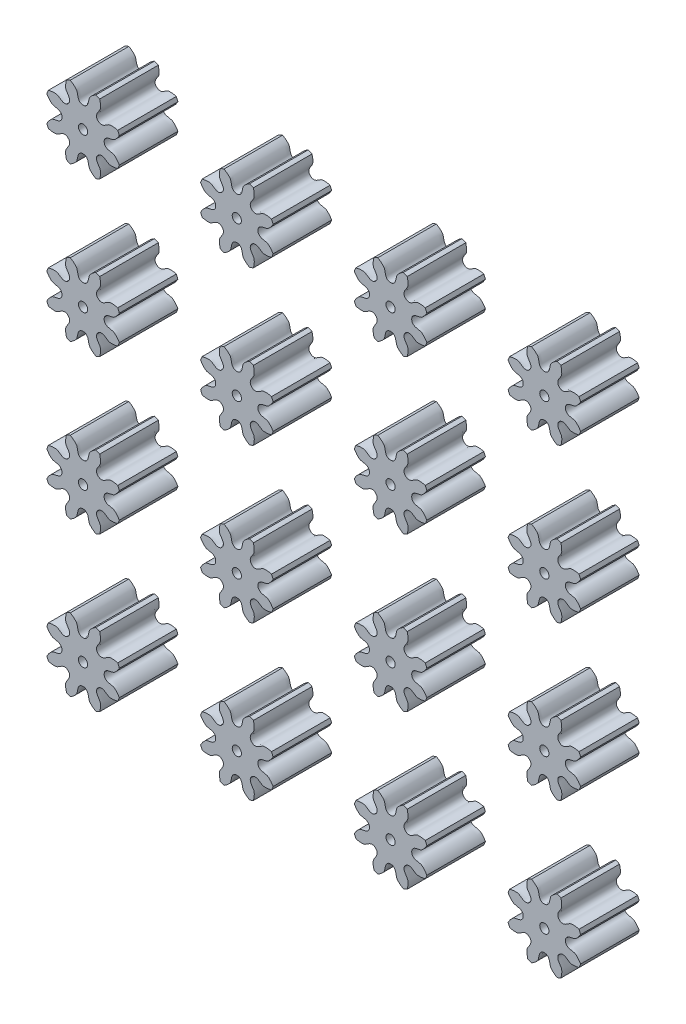
SolidWorks part; units mm, degrees
ref_plane "前视基准面" through (0, 0, 0) normal (0, 0, 1) x (1, 0, 0)
ref_plane "上视基准面" through (0, 0, 0) normal (0, 1, 0) x (1, 0, 0)
ref_plane "右视基准面" through (0, 0, 0) normal (1, 0, 0) x (0, 0, -1)
ref_axis "基准轴1" through (0, 0, 55) along (0, 0, -1)
sketch "SketchRevolveSpurGear1" plane through (0, 0, 0) normal (1, 0, 0) x (0, 0, -1)
  line L0 (0, 0) -> (1, 0) construction
  line L1 (-9.525, 0) -> (-9.525, 12.5)
  line L2 (-9.525, 12.5) -> (9.525, 12.5)
  line L3 (9.525, 12.5) -> (9.525, 0)
  line L4 (9.525, 0) -> (-9.525, 0)
revolve "SpurGear1" add sketch "SketchRevolveSpurGear1" angle 360 about L0
sketch "SketchToothSpurGear1" plane through (0, 0, 0) normal (0, 0, 1) x (1, 0, 0)
  arc A0 (11.8708, 4.2983) -> (11.8708, -4.2983) centre (0, 0) cw
  spline S0 degree 3 poles (11.8708, -4.2983) (11.7054, -3.9899) (11.4661, -3.6029) (11.1329, -3.1632) (10.9456, -2.9376) (10.7609, -2.7348) (10.581, -2.5534) (10.4063, -2.3946) (9.7527, -1.8246) (8.8695, -1.8284) (8.1725, -1.6298) (8.1519, -1.6237) (8.1313, -1.6175) (8.1108, -1.6111) (8.0904, -1.6045) (8.0701, -1.5977) (8.0499, -1.5908) (8.0297, -1.5837) (8.0096, -1.5764) (7.9897, -1.569) (7.9698, -1.5614) (7.95, -1.5536) (7.9302, -1.5456) (7.9106, -1.5375) (7.891, -1.5291) (7.8716, -1.5206) (7.8522, -1.5119) (7.8329, -1.503) (7.8137, -1.4939) (7.7946, -1.4847) (7.7756, -1.4752) (7.7567, -1.4655) (7.7378, -1.4557) (7.7191, -1.4456) (7.7005, -1.4354) (7.6819, -1.4249) (7.6635, -1.4142) (7.6451, -1.4033) (7.6269, -1.3922) (7.6087, -1.3809) (7.5907, -1.3694) (7.5728, -1.3577) (7.5549, -1.3457) (7.5372, -1.3335) (7.5196, -1.3211) (7.5021, -1.3084) (7.4848, -1.2955) (7.4675, -1.2824) (7.4504, -1.269) (7.4334, -1.2554) (7.4165, -1.2416) (7.3998, -1.2275) (7.3832, -1.2131) (7.3667, -1.1985) (7.3504, -1.1836) (7.3342, -1.1685) (7.3182, -1.1531) (7.3024, -1.1375) (7.2867, -1.1215) (7.2711, -1.1053) (7.2558, -1.0889) (7.2406, -1.0721) (7.2257, -1.0551) (7.2109, -1.0378) (7.1963, -1.0202) (7.1819, -1.0023) (7.1677, -0.9841) (7.1538, -0.9657) (7.1401, -0.947) (7.1266, -0.9279) (7.1134, -0.9086) (7.1004, -0.889) (7.0877, -0.8691) (7.0752, -0.849) (7.063, -0.8285) (7.0511, -0.8078) (7.0396, -0.7867) (7.0283, -0.7654) (7.0173, -0.7438) (7.0067, -0.722) (6.9964, -0.6999) (6.9865, -0.6775) (6.9769, -0.6548) (6.9677, -0.6319) (6.9588, -0.6088) (6.9503, -0.5854) (6.9423, -0.5618) (6.9346, -0.5379) (6.9274, -0.5138) (6.9206, -0.4896) (6.9142, -0.4651) (6.9083, -0.4405) (6.9028, -0.4156) (6.8977, -0.3907) (6.8932, -0.3655) (6.8891, -0.3403) (6.8854, -0.3149) (6.8823, -0.2894) (6.8796, -0.2638) (6.8775, -0.2381) (6.8758, -0.2123) (6.8746, -0.1865) (6.874, -0.1607) (6.8738, -0.1374) (6.8743, -0.0838) (6.8756, 0) (6.8743, 0.0838) (6.8738, 0.1374) (6.874, 0.1607) (6.8746, 0.1865) (6.8758, 0.2123) (6.8775, 0.2381) (6.8796, 0.2638) (6.8823, 0.2894) (6.8854, 0.3149) (6.8891, 0.3403) (6.8932, 0.3655) (6.8977, 0.3907) (6.9028, 0.4156) (6.9083, 0.4405) (6.9142, 0.4651) (6.9206, 0.4896) (6.9274, 0.5138) (6.9346, 0.5379) (6.9423, 0.5618) (6.9503, 0.5854) (6.9588, 0.6088) (6.9677, 0.6319) (6.9769, 0.6548) (6.9865, 0.6775) (6.9964, 0.6999) (7.0067, 0.722) (7.0173, 0.7438) (7.0283, 0.7654) (7.0396, 0.7867) (7.0511, 0.8078) (7.063, 0.8285) (7.0752, 0.849) (7.0877, 0.8691) (7.1004, 0.889) (7.1134, 0.9086) (7.1266, 0.9279) (7.1401, 0.947) (7.1538, 0.9657) (7.1677, 0.9841) (7.1819, 1.0023) (7.1963, 1.0202) (7.2109, 1.0378) (7.2257, 1.0551) (7.2406, 1.0721) (7.2558, 1.0889) (7.2711, 1.1053) (7.2867, 1.1215) (7.3024, 1.1375) (7.3182, 1.1531) (7.3342, 1.1685) (7.3504, 1.1836) (7.3667, 1.1985) (7.3832, 1.2131) (7.3998, 1.2275) (7.4165, 1.2416) (7.4334, 1.2554) (7.4504, 1.269) (7.4675, 1.2824) (7.4848, 1.2955) (7.5021, 1.3084) (7.5196, 1.3211) (7.5372, 1.3335) (7.5549, 1.3457) (7.5728, 1.3577) (7.5907, 1.3694) (7.6087, 1.3809) (7.6269, 1.3922) (7.6451, 1.4033) (7.6635, 1.4142) (7.6819, 1.4249) (7.7005, 1.4354) (7.7191, 1.4456) (7.7378, 1.4557) (7.7567, 1.4655) (7.7756, 1.4752) (7.7946, 1.4847) (7.8137, 1.4939) (7.8329, 1.503) (7.8522, 1.5119) (7.8716, 1.5206) (7.891, 1.5291) (7.9106, 1.5375) (7.9302, 1.5456) (7.95, 1.5536) (7.9698, 1.5614) (7.9897, 1.569) (8.0096, 1.5764) (8.0297, 1.5837) (8.0499, 1.5908) (8.0701, 1.5977) (8.0904, 1.6045) (8.1108, 1.6111) (8.1313, 1.6175) (8.1519, 1.6237) (8.1725, 1.6298) (8.8695, 1.8284) (9.7527, 1.8246) (10.4063, 2.3946) (10.581, 2.5534) (10.7609, 2.7348) (10.9456, 2.9376) (11.1329, 3.1632) (11.4661, 3.6029) (11.7054, 3.9899) (11.8708, 4.2983) knots 0 0 0 0 0.074363 0.096474 0.117246 0.136677 0.154768 0.17152 0.186931 0.337992 0.33952 0.341045 0.342568 0.344089 0.345608 0.347125 0.34864 0.350154 0.351666 0.353177 0.354686 0.356194 0.357702 0.359209 0.360715 0.36222 0.363725 0.36523 0.366735 0.36824 0.369745 0.37125 0.372757 0.374264 0.375771 0.37728 0.37879 0.380302 0.381815 0.38333 0.384847 0.386366 0.387888 0.389412 0.390939 0.392468 0.394001 0.395537 0.397077 0.39862 0.400167 0.401717 0.403273 0.404832 0.406396 0.407965 0.409539 0.411118 0.412702 0.414292 0.415887 0.417488 0.419095 0.420708 0.422328 0.423953 0.425585 0.427224 0.428869 0.430521 0.43218 0.433846 0.435519 0.437199 0.438886 0.44058 0.442281 0.443989 0.445704 0.447427 0.449156 0.450892 0.452635 0.454385 0.456141 0.457903 0.459672 0.461447 0.463227 0.465013 0.466805 0.468601 0.470403 0.472209 0.474019 0.475833 0.477651 0.479471 0.481295 0.483121 0.48495 0.48678 0.488611 0.490443 0.491735 0.5 0.508265 0.509557 0.511389 0.51322 0.51505 0.516879 0.518705 0.520529 0.522349 0.524167 0.525981 0.527791 0.529597 0.531399 0.533195 0.534987 0.536773 0.538553 0.540328 0.542097 0.543859 0.545615 0.547365 0.549108 0.550844 0.552573 0.554296 0.556011 0.557719 0.55942 0.561114 0.562801 0.564481 0.566154 0.56782 0.569479 0.571131 0.572776 0.574415 0.576047 0.577672 0.579292 0.580905 0.582512 0.584113 0.585708 0.587298 0.588882 0.590461 0.592035 0.593604 0.595168 0.596727 0.598283 0.599833 0.60138 0.602923 0.604463 0.605999 0.607532 0.609061 0.610588 0.612112 0.613634 0.615153 0.61667 0.618185 0.619698 0.62121 0.62272 0.624229 0.625736 0.627243 0.62875 0.630255 0.63176 0.633265 0.63477 0.636275 0.63778 0.639285 0.640791 0.642298 0.643806 0.645314 0.646823 0.648334 0.649846 0.65136 0.652875 0.654392 0.655911 0.657432 0.658955 0.66048 0.662008 0.813069 0.82848 0.845232 0.863323 0.882754 0.903526 0.925637 1 1 1 1
extrude "ToothExtrudeCutSpurGear1" cut sketch "SketchToothSpurGear1" against normal blind 9.525 and the other way blind 9.525
pattern_circular "PatternSpurGear1" count 8 every 45 about axis through (0, 0, 55) along (0, 0, -1) of "ToothExtrudeCutSpurGear1"
sketch "BoreRevolveSketch" plane through (0, 0, 0) normal (1, 0, 0) x (0, 0, -1)
  line L0 (0, 0) -> (1, 0) construction
  line L1 (-9.525, 0) -> (9.525, 0)
  line L2 (9.525, 0) -> (9.525, 1.5)
  line L3 (9.525, 1.5) -> (-9.525, 1.5)
  line L4 (-9.525, 1.5) -> (-9.525, 0)
  dimension "TaperSide1" = 1.5
  dimension "TaperSide2" = 1.5
revolve "BoreRevolveCut" cut sketch "BoreRevolveSketch" angle 360 about L0
sketch "AuxiliarySketchSpurGear1" plane through (0, 0, 0) normal (0, 0, 1) x (1, 0, 0)
  circle A0 centre (0, 0) radius 10 construction
  circle A1 centre (0, 0) radius 9.3969 construction
  circle A2 centre (0, 0) radius 10.1791 construction
  circle A3 centre (0, 0) radius 12.5 construction
  circle A4 centre (0, 0) radius 6.875 construction
  dimension "PitchDiameter" = 20
  dimension "BaseDiameter" = 18.7939
  dimension "FormDiameter" = 20.3583
  dimension "MajorDiameter" = 25
  dimension "MinorDiameter" = 13.75
scale "缩放比例1" scale about origin uniform scaling yes scale factor 0.2
pattern_linear "阵列(线性)1" count 4 spacing 10 along (1, 0, 0) count 4 spacing 10 along (0, 1, 0) of bodies 105
